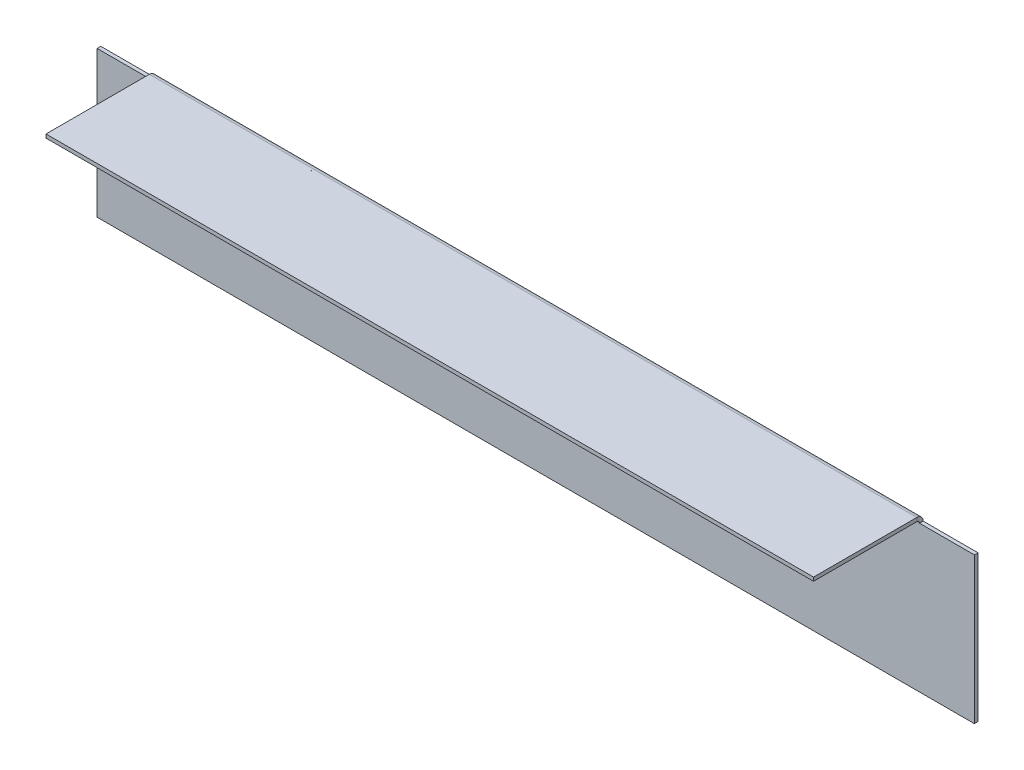
SolidWorks part; units mm, degrees
note: The reader was unsure of these and kept them because the rebuilt part matched: flange length of "边线-法兰1".
ref_plane "前视基准面" through (0, 0, 0) normal (0, 0, 1) x (1, 0, 0)
ref_plane "上视基准面" through (0, 0, 0) normal (0, 1, 0) x (1, 0, 0)
ref_plane "右视基准面" through (0, 0, 0) normal (1, 0, 0) x (0, 0, -1)
sketch "草图1" plane through (0, 0, 0) normal (0, 0, 1) x (1, 0, 0)
  line L1 (-120, -20) -> (120, -20)
  line L2 (-120, -20) -> (-120, 20)
  line L3 (-120, 20) -> (120, 20)
  line L4 (120, -20) -> (120, 20)
  line L5 (-120, -20) -> (120, 20) construction
  line L6 (-120, 20) -> (120, -20) construction
  point P0 (0, 0)
  dimension "D1" = 240
  dimension "D2" = 40
base flange "基体-法兰1" sketch "草图1" thickness 1 reverse thickness direction no parameters "D1"=0.7366
edge flange "边线-法兰1" sketch "草图8" flange angle 90 flange length 30 flange position bend outside bend radius 0.7366 thickness 1 relief rectangular parameters "D6"=10
sketch "草图8" plane through (0, 20, 0) normal (0, -1, 0) x (1, 0, 0)
  line L1 (120, 0) -> (-120, 0) construction
  line L2 (-105, 0) -> (-105, 29)
  line L3 (-105, 29) -> (105, 29)
  line L4 (105, 29) -> (105, 0)
  line L5 (105, 0) -> (-105, 0)
  dimension "D1" = 15
  dimension "D2" = 15
bend "边线折弯1" bend radius 0.7366 bend angle 90 parameters "D5"=1
sketch "折弯-线1" plane through (0, 0, 0) normal (0, 1, 0) x (1, 0, 0)
sketch "边界框1" plane through (0, 0, 0) normal (0, 1, 0) x (1, 0, 0)
sheet metal parameters "钣金6" thickness 1 parameters "D1"=0.7366
flat pattern "平板型式6" [suppressed]
sketch "折弯-线2" plane through (0, 0, 0) normal (0, 1, 0) x (1, 0, 0)
sketch "边界框2" [suppressed] plane through (0, 0, 0) normal (0, 1, 0) x (1, 0, 0)
sheet metal parameters "钣金7" thickness 1 parameters "D1"=0.7366
flat pattern "平板型式6" [suppressed]
sketch "折弯-线2" plane through (0, 0, 0) normal (0, 1, 0) x (1, 0, 0)
sketch "边界框2" [suppressed] plane through (0, 0, 0) normal (0, 1, 0) x (1, 0, 0)
bend of the flat pattern "展开-<边线折弯1>1"
